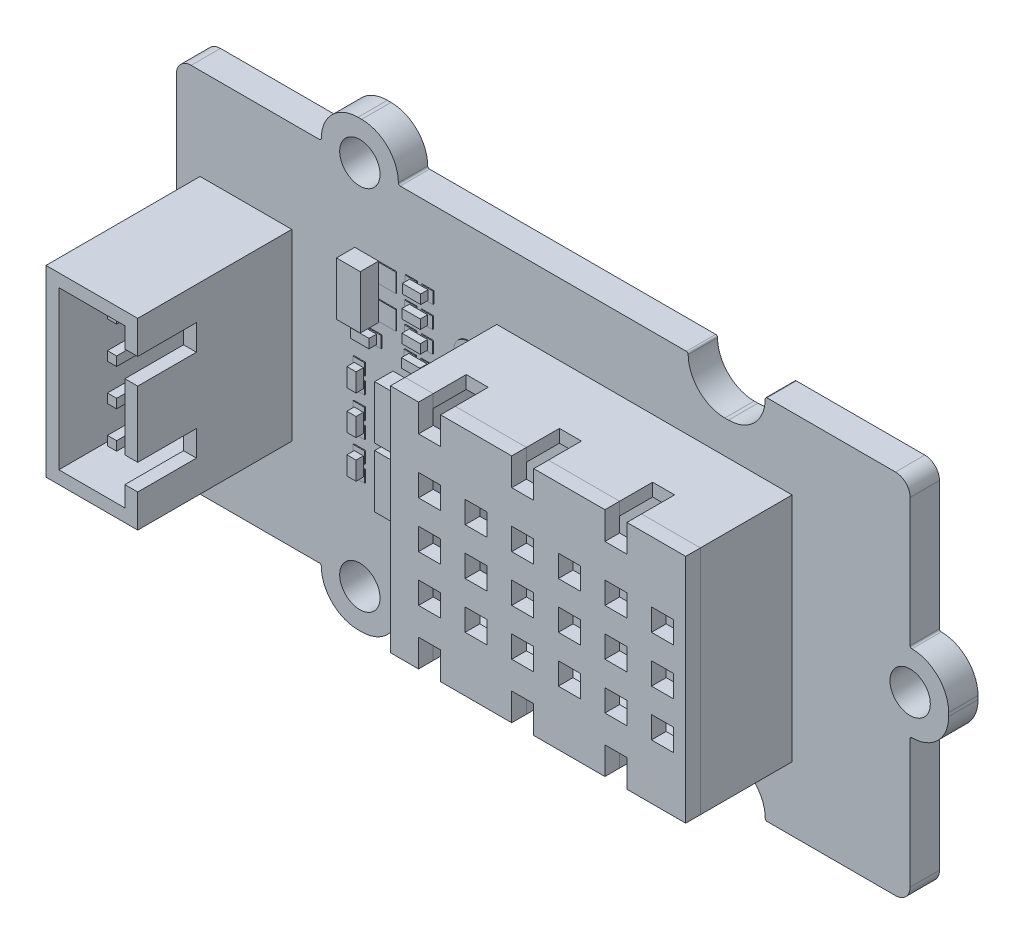
SolidWorks part; units mm, degrees
other "PCB_Grove_101020932"
ref_plane "Plan de face" through (0, 0, 0) normal (0, 0, 1) x (1, 0, 0)
ref_plane "Plan de dessus" through (0, 0, 0) normal (0, 1, 0) x (1, 0, 0)
ref_plane "Plan de droite" through (0, 0, 0) normal (1, 0, 0) x (0, 0, -1)
sketch "Esquisse1" plane through (0, 0, 0) normal (0, 0, 1) x (1, 0, 0)
  line L0 (-12.2, 10) -> (-19.2, 10)
  line L1 (-20, 9.2) -> (-20, 2.2)
  line L2 (-17.9, 0.1) -> (-17.9, -0.1)
  line L3 (-20, -2.2) -> (-20, -9.2)
  line L4 (-19.2, -10) -> (-12.2, -10)
  line L5 (-10.1, -12.1) -> (-9.9, -12.1)
  line L6 (-7.8, -10) -> (7.8, -10)
  line L7 (9.9, -7.9) -> (10.1, -7.9)
  line L8 (12.2, -10) -> (19.2, -10)
  line L9 (20, -9.2) -> (20, -2.2)
  line L10 (22.1, -0.1) -> (22.1, 0.1)
  line L11 (20, 2.2) -> (20, 9.2)
  line L12 (19.2, 10) -> (12.2, 10)
  line L13 (10.1, 7.9) -> (9.9, 7.9)
  line L14 (7.8, 10) -> (-7.8, 10)
  line L15 (-9.9, 12.1) -> (-10.1, 12.1)
  arc A0 (-19.2, 10) -> (-20, 9.2) centre (-19.2, 9.2) ccw
  arc A1 (-20, 2.2) -> (-19.9, 2.1) centre (-19.9, 2.2) ccw
  arc A2 (-19.9, 2.1) -> (-17.9, 0.1) centre (-19.9, 0.1) cw
  arc A3 (-17.9, -0.1) -> (-19.9, -2.1) centre (-19.9, -0.1) cw
  arc A4 (-19.9, -2.1) -> (-20, -2.2) centre (-19.9, -2.2) ccw
  arc A5 (-20, -9.2) -> (-19.2, -10) centre (-19.2, -9.2) ccw
  arc A6 (-12.2, -10) -> (-12.1, -10.1) centre (-12.2, -10.1) cw
  arc A7 (-12.1, -10.1) -> (-10.1, -12.1) centre (-10.1, -10.1) ccw
  arc A8 (-9.9, -12.1) -> (-7.9, -10.1) centre (-9.9, -10.1) ccw
  arc A9 (-7.9, -10.1) -> (-7.8, -10) centre (-7.8, -10.1) cw
  arc A10 (7.8, -10) -> (7.9, -9.9) centre (7.8, -9.9) ccw
  arc A11 (7.9, -9.9) -> (9.9, -7.9) centre (9.9, -9.9) cw
  arc A12 (10.1, -7.9) -> (12.1, -9.9) centre (10.1, -9.9) cw
  arc A13 (12.1, -9.9) -> (12.2, -10) centre (12.2, -9.9) ccw
  arc A14 (19.2, -10) -> (20, -9.2) centre (19.2, -9.2) ccw
  arc A15 (20, -2.2) -> (20.1, -2.1) centre (20.1, -2.2) cw
  arc A16 (20.1, -2.1) -> (22.1, -0.1) centre (20.1, -0.1) ccw
  arc A17 (22.1, 0.1) -> (20.1, 2.1) centre (20.1, 0.1) ccw
  arc A18 (20.1, 2.1) -> (20, 2.2) centre (20.1, 2.2) cw
  arc A19 (20, 9.2) -> (19.2, 10) centre (19.2, 9.2) ccw
  arc A20 (12.2, 10) -> (12.1, 9.9) centre (12.2, 9.9) ccw
  arc A21 (12.1, 9.9) -> (10.1, 7.9) centre (10.1, 9.9) cw
  arc A22 (9.9, 7.9) -> (7.9, 9.9) centre (9.9, 9.9) cw
  arc A23 (7.9, 9.9) -> (7.8, 10) centre (7.8, 9.9) ccw
  arc A24 (-7.8, 10) -> (-7.9, 10.1) centre (-7.8, 10.1) cw
  arc A25 (-7.9, 10.1) -> (-9.9, 12.1) centre (-9.9, 10.1) ccw
  arc A26 (-10.1, 12.1) -> (-12.1, 10.1) centre (-10.1, 10.1) ccw
  arc A27 (-12.1, 10.1) -> (-12.2, 10) centre (-12.2, 10.1) cw
  circle A28 centre (-10, -10) radius 1.1
  circle A29 centre (-10, 10) radius 1.1
  circle A30 centre (20, 0) radius 1.1
  circle A31 centre (-16.51, -3) radius 0.4
  circle A32 centre (-16.51, -1) radius 0.4
  circle A33 centre (-16.51, 1) radius 0.4
  circle A34 centre (-16.51, 3) radius 0.4
  circle A35 centre (-4.064, 3.81) radius 0.4445
  circle A36 centre (-4.064, 1.27) radius 0.4445
  circle A37 centre (-4.064, -1.27) radius 0.4445
  circle A38 centre (-4.064, -3.81) radius 0.4445
extrude "PCB_Eagle_V2_1_ep_ESTIMEE_1_6" add sketch "Esquisse1" along normal blind 1.6 separate body
sketch "Esquisse2" plane through (0, 0, 0) normal (0, 0, 1) x (1, 0, 0)
  line L1 (-18.71, -5) -> (-13.71, -5)
  line L2 (-18.71, -5) -> (-18.71, 5)
  line L3 (-18.71, 5) -> (-13.71, 5)
  line L4 (-13.71, -5) -> (-13.71, 5)
extrude "Grove_vertical_H_ESTIMEE" add sketch "Esquisse2" along normal blind 8.4 from offset 1.6 separate body
sketch "Esquisse3" plane through (0, 0, 0) normal (0, 0, 1) x (1, 0, 0)
  line L1 (-18.01, -4.3) -> (-14.41, -4.3)
  line L2 (-18.01, -4.3) -> (-18.01, 4.3)
  line L3 (-18.01, 4.3) -> (-14.41, 4.3)
  line L4 (-14.41, -4.3) -> (-14.41, 4.3)
extrude "Cavite_Grove" cut sketch "Esquisse3" against normal blind 7.3 from offset 10
sketch "Esquisse4" plane through (0, 0, 0) normal (0, 0, 1) x (1, 0, 0)
  line L1 (-14.51, -3.2) -> (-13.51, -3.2)
  line L2 (-14.51, -3.2) -> (-14.51, -1.8)
  line L3 (-14.51, -1.8) -> (-13.51, -1.8)
  line L4 (-13.51, -3.2) -> (-13.51, -1.8)
  line L6 (-14.51, 1.8) -> (-13.51, 1.8)
  line L7 (-14.51, 1.8) -> (-14.51, 3.2)
  line L8 (-14.51, 3.2) -> (-13.51, 3.2)
  line L9 (-13.51, 1.8) -> (-13.51, 3.2)
extrude "Detrompeurs_Grove" cut sketch "Esquisse4" against normal blind 3.2 from offset 10
sketch "Esquisse5" plane through (0, 0, 0) normal (0, 0, 1) x (1, 0, 0)
  line L1 (-16.76, -3.25) -> (-16.26, -3.25)
  line L2 (-16.76, -3.25) -> (-16.76, -2.75)
  line L3 (-16.76, -2.75) -> (-16.26, -2.75)
  line L4 (-16.26, -3.25) -> (-16.26, -2.75)
  line L6 (-16.76, -1.25) -> (-16.26, -1.25)
  line L7 (-16.76, -1.25) -> (-16.76, -0.75)
  line L8 (-16.76, -0.75) -> (-16.26, -0.75)
  line L9 (-16.26, -1.25) -> (-16.26, -0.75)
  line L11 (-16.76, 0.75) -> (-16.26, 0.75)
  line L12 (-16.76, 0.75) -> (-16.76, 1.25)
  line L13 (-16.76, 1.25) -> (-16.26, 1.25)
  line L14 (-16.26, 0.75) -> (-16.26, 1.25)
  line L16 (-16.76, 2.75) -> (-16.26, 2.75)
  line L17 (-16.76, 2.75) -> (-16.76, 3.25)
  line L18 (-16.76, 3.25) -> (-16.26, 3.25)
  line L19 (-16.26, 2.75) -> (-16.26, 3.25)
extrude "Contacts_Grove" add sketch "Esquisse5" along normal blind 9.4 from offset 0.8 separate body
sketch "Esquisse6" plane through (0, 0, 0) normal (0, 0, 1) x (1, 0, 0)
  line L1 (-2.335, -6.3) -> (13.765, -6.3)
  line L2 (-2.335, -6.3) -> (-2.335, 6.3)
  line L3 (-2.335, 6.3) -> (13.765, 6.3)
  line L4 (13.765, -6.3) -> (13.765, 6.3)
extrude "DHT20_enveloppe_16_1x12_6x5_8" add sketch "Esquisse6" along normal blind 5 from offset 1.8 separate body
sketch "Esquisse7" plane through (0, 0, 0) normal (0, 0, 1) x (1, 0, 0)
  line L1 (-1.635, -5.6) -> (13.065, -5.6)
  line L2 (-1.635, -5.6) -> (-1.635, 5.6)
  line L3 (-1.635, 5.6) -> (13.065, 5.6)
  line L4 (13.065, -5.6) -> (13.065, 5.6)
extrude "DHT20_interieur_simplifie" cut sketch "Esquisse7" against normal blind 4.4 from offset 6.8
sketch "Esquisse8" plane through (0, 0, 0) normal (0, 0, 1) x (1, 0, 0)
  line L1 (-2.335, -6.3) -> (13.765, -6.3)
  line L2 (-2.335, -6.3) -> (-2.335, 6.3)
  line L3 (-2.335, 6.3) -> (13.765, 6.3)
  line L4 (13.765, -6.3) -> (13.765, 6.3)
  line L6 (-0.8, -3.3) -> (0.4, -3.3)
  line L7 (-0.8, -3.3) -> (-0.8, -2.1)
  line L8 (-0.8, -2.1) -> (0.4, -2.1)
  line L9 (0.4, -3.3) -> (0.4, -2.1)
  line L11 (-0.8, -0.76) -> (0.4, -0.76)
  line L12 (-0.8, -0.76) -> (-0.8, 0.44)
  line L13 (-0.8, 0.44) -> (0.4, 0.44)
  line L14 (0.4, -0.76) -> (0.4, 0.44)
  line L16 (-0.8, 1.78) -> (0.4, 1.78)
  line L17 (-0.8, 1.78) -> (-0.8, 2.98)
  line L18 (-0.8, 2.98) -> (0.4, 2.98)
  line L19 (0.4, 1.78) -> (0.4, 2.98)
  line L21 (1.74, -3.3) -> (2.94, -3.3)
  line L22 (1.74, -3.3) -> (1.74, -2.1)
  line L23 (1.74, -2.1) -> (2.94, -2.1)
  line L24 (2.94, -3.3) -> (2.94, -2.1)
  line L26 (1.74, -0.76) -> (2.94, -0.76)
  line L27 (1.74, -0.76) -> (1.74, 0.44)
  line L28 (1.74, 0.44) -> (2.94, 0.44)
  line L29 (2.94, -0.76) -> (2.94, 0.44)
  line L31 (1.74, 1.78) -> (2.94, 1.78)
  line L32 (1.74, 1.78) -> (1.74, 2.98)
  line L33 (1.74, 2.98) -> (2.94, 2.98)
  line L34 (2.94, 1.78) -> (2.94, 2.98)
  line L36 (4.28, -3.3) -> (5.48, -3.3)
  line L37 (4.28, -3.3) -> (4.28, -2.1)
  line L38 (4.28, -2.1) -> (5.48, -2.1)
  line L39 (5.48, -3.3) -> (5.48, -2.1)
  line L41 (4.28, -0.76) -> (5.48, -0.76)
  line L42 (4.28, -0.76) -> (4.28, 0.44)
  line L43 (4.28, 0.44) -> (5.48, 0.44)
  line L44 (5.48, -0.76) -> (5.48, 0.44)
  line L46 (4.28, 1.78) -> (5.48, 1.78)
  line L47 (4.28, 1.78) -> (4.28, 2.98)
  line L48 (4.28, 2.98) -> (5.48, 2.98)
  line L49 (5.48, 1.78) -> (5.48, 2.98)
  line L51 (6.82, -3.3) -> (8.02, -3.3)
  line L52 (6.82, -3.3) -> (6.82, -2.1)
  line L53 (6.82, -2.1) -> (8.02, -2.1)
  line L54 (8.02, -3.3) -> (8.02, -2.1)
  line L56 (6.82, -0.76) -> (8.02, -0.76)
  line L57 (6.82, -0.76) -> (6.82, 0.44)
  line L58 (6.82, 0.44) -> (8.02, 0.44)
  line L59 (8.02, -0.76) -> (8.02, 0.44)
  line L61 (6.82, 1.78) -> (8.02, 1.78)
  line L62 (6.82, 1.78) -> (6.82, 2.98)
  line L63 (6.82, 2.98) -> (8.02, 2.98)
  line L64 (8.02, 1.78) -> (8.02, 2.98)
  line L66 (9.36, -3.3) -> (10.56, -3.3)
  line L67 (9.36, -3.3) -> (9.36, -2.1)
  line L68 (9.36, -2.1) -> (10.56, -2.1)
  line L69 (10.56, -3.3) -> (10.56, -2.1)
  line L71 (9.36, -0.76) -> (10.56, -0.76)
  line L72 (9.36, -0.76) -> (9.36, 0.44)
  line L73 (9.36, 0.44) -> (10.56, 0.44)
  line L74 (10.56, -0.76) -> (10.56, 0.44)
  line L76 (9.36, 1.78) -> (10.56, 1.78)
  line L77 (9.36, 1.78) -> (9.36, 2.98)
  line L78 (9.36, 2.98) -> (10.56, 2.98)
  line L79 (10.56, 1.78) -> (10.56, 2.98)
  line L81 (11.9, -3.3) -> (13.1, -3.3)
  line L82 (11.9, -3.3) -> (11.9, -2.1)
  line L83 (11.9, -2.1) -> (13.1, -2.1)
  line L84 (13.1, -3.3) -> (13.1, -2.1)
  line L86 (11.9, -0.76) -> (13.1, -0.76)
  line L87 (11.9, -0.76) -> (11.9, 0.44)
  line L88 (11.9, 0.44) -> (13.1, 0.44)
  line L89 (13.1, -0.76) -> (13.1, 0.44)
  line L91 (11.9, 1.78) -> (13.1, 1.78)
  line L92 (11.9, 1.78) -> (11.9, 2.98)
  line L93 (11.9, 2.98) -> (13.1, 2.98)
  line L94 (13.1, 1.78) -> (13.1, 2.98)
extrude "DHT20_grille_aeration_simplifiee" add sketch "Esquisse8" along normal blind 0.8 from offset 6.8 separate body
sketch "Esquisse9" plane through (0, 0, 0) normal (0, 0, 1) x (1, 0, 0)
  line L1 (-0.8, -6.4) -> (0.4, -6.4)
  line L2 (-0.8, -6.4) -> (-0.8, -4.8)
  line L3 (-0.8, -4.8) -> (0.4, -4.8)
  line L4 (0.4, -6.4) -> (0.4, -4.8)
  line L6 (-0.8, 4.8) -> (0.4, 4.8)
  line L7 (-0.8, 4.8) -> (-0.8, 6.4)
  line L8 (-0.8, 6.4) -> (0.4, 6.4)
  line L9 (0.4, 4.8) -> (0.4, 6.4)
  line L11 (4.28, -6.4) -> (5.48, -6.4)
  line L12 (4.28, -6.4) -> (4.28, -4.8)
  line L13 (4.28, -4.8) -> (5.48, -4.8)
  line L14 (5.48, -6.4) -> (5.48, -4.8)
  line L16 (4.28, 4.8) -> (5.48, 4.8)
  line L17 (4.28, 4.8) -> (4.28, 6.4)
  line L18 (4.28, 6.4) -> (5.48, 6.4)
  line L19 (5.48, 4.8) -> (5.48, 6.4)
  line L21 (9.36, -6.4) -> (10.56, -6.4)
  line L22 (9.36, -6.4) -> (9.36, -4.8)
  line L23 (9.36, -4.8) -> (10.56, -4.8)
  line L24 (10.56, -6.4) -> (10.56, -4.8)
  line L26 (9.36, 4.8) -> (10.56, 4.8)
  line L27 (9.36, 4.8) -> (9.36, 6.4)
  line L28 (9.36, 6.4) -> (10.56, 6.4)
  line L29 (10.56, 4.8) -> (10.56, 6.4)
extrude "DHT20_encoches_laterales" cut sketch "Esquisse9" against normal blind 2.6 from offset 7.6
sketch "Esquisse10" plane through (0, 0, 0) normal (0, 0, 1) x (1, 0, 0)
  line L1 (-4.314, -4.06) -> (-2.335, -4.06)
  line L2 (-4.314, -4.06) -> (-4.314, -3.56)
  line L3 (-4.314, -3.56) -> (-2.335, -3.56)
  line L4 (-2.335, -4.06) -> (-2.335, -3.56)
  line L6 (-4.314, -1.52) -> (-2.335, -1.52)
  line L7 (-4.314, -1.52) -> (-4.314, -1.02)
  line L8 (-4.314, -1.02) -> (-2.335, -1.02)
  line L9 (-2.335, -1.52) -> (-2.335, -1.02)
  line L11 (-4.314, 1.02) -> (-2.335, 1.02)
  line L12 (-4.314, 1.02) -> (-4.314, 1.52)
  line L13 (-4.314, 1.52) -> (-2.335, 1.52)
  line L14 (-2.335, 1.02) -> (-2.335, 1.52)
  line L16 (-4.314, 3.56) -> (-2.335, 3.56)
  line L17 (-4.314, 3.56) -> (-4.314, 4.06)
  line L18 (-4.314, 4.06) -> (-2.335, 4.06)
  line L19 (-2.335, 3.56) -> (-2.335, 4.06)
extrude "Pattes_DHT20_horizontales" add sketch "Esquisse10" along normal blind 0.3 from offset 4.05 separate body
sketch "Esquisse11" plane through (0, 0, 0) normal (0, 0, 1) x (1, 0, 0)
  line L1 (-4.314, -4.06) -> (-3.814, -4.06)
  line L2 (-4.314, -4.06) -> (-4.314, -3.56)
  line L3 (-4.314, -3.56) -> (-3.814, -3.56)
  line L4 (-3.814, -4.06) -> (-3.814, -3.56)
  line L6 (-4.314, -1.52) -> (-3.814, -1.52)
  line L7 (-4.314, -1.52) -> (-4.314, -1.02)
  line L8 (-4.314, -1.02) -> (-3.814, -1.02)
  line L9 (-3.814, -1.52) -> (-3.814, -1.02)
  line L11 (-4.314, 1.02) -> (-3.814, 1.02)
  line L12 (-4.314, 1.02) -> (-4.314, 1.52)
  line L13 (-4.314, 1.52) -> (-3.814, 1.52)
  line L14 (-3.814, 1.02) -> (-3.814, 1.52)
  line L16 (-4.314, 3.56) -> (-3.814, 3.56)
  line L17 (-4.314, 3.56) -> (-4.314, 4.06)
  line L18 (-4.314, 4.06) -> (-3.814, 4.06)
  line L19 (-3.814, 3.56) -> (-3.814, 4.06)
extrude "Pattes_DHT20_traversantes" add sketch "Esquisse11" along normal blind 4.85 from offset 0.8 separate body
sketch "Esquisse12" plane through (0, 0, 0) normal (0, 0, 1) x (1, 0, 0)
  line L1 (-10.2258, 3.0204) -> (-8.9258, 3.0204)
  line L2 (-10.2258, 3.0204) -> (-10.2258, 5.9204)
  line L3 (-10.2258, 5.9204) -> (-8.9258, 5.9204)
  line L4 (-8.9258, 3.0204) -> (-8.9258, 5.9204)
extrude "U14_position_Eagle" add sketch "Esquisse12" along normal blind 1 from offset 1.65 separate body
sketch "Esquisse13" plane through (0, 0, 0) normal (0, 0, 1) x (1, 0, 0)
  line L1 (-10.0504, 1.909) -> (-9.0504, 1.909)
  line L2 (-10.0504, 1.909) -> (-10.0504, 2.409)
  line L3 (-10.0504, 2.409) -> (-9.0504, 2.409)
  line L4 (-9.0504, 1.909) -> (-9.0504, 2.409)
extrude "C62_position_Eagle" add sketch "Esquisse13" along normal blind 0.4 from offset 1.65 separate body
sketch "Esquisse14" plane through (0, 0, 0) normal (0, 0, 1) x (1, 0, 0)
  line L1 (-7.231, 5.4142) -> (-6.231, 5.4142)
  line L2 (-7.231, 5.4142) -> (-7.231, 5.9142)
  line L3 (-7.231, 5.9142) -> (-6.231, 5.9142)
  line L4 (-6.231, 5.4142) -> (-6.231, 5.9142)
extrude "C65_position_Eagle" add sketch "Esquisse14" along normal blind 0.4 from offset 1.65 separate body
sketch "Esquisse15" plane through (0, 0, 0) normal (0, 0, 1) x (1, 0, 0)
  line L1 (-8.143, -1.7802) -> (-6.843, -1.7802)
  line L2 (-8.143, -1.7802) -> (-8.143, 1.1198)
  line L3 (-8.143, 1.1198) -> (-6.843, 1.1198)
  line L4 (-6.843, -1.7802) -> (-6.843, 1.1198)
extrude "Q12_position_Eagle" add sketch "Esquisse15" along normal blind 1 from offset 1.65 separate body
sketch "Esquisse16" plane through (0, 0, 0) normal (0, 0, 1) x (1, 0, 0)
  line L1 (-8.143, -5.0314) -> (-6.843, -5.0314)
  line L2 (-8.143, -5.0314) -> (-8.143, -2.1314)
  line L3 (-8.143, -2.1314) -> (-6.843, -2.1314)
  line L4 (-6.843, -5.0314) -> (-6.843, -2.1314)
extrude "Q13_position_Eagle" add sketch "Esquisse16" along normal blind 1 from offset 1.65 separate body
sketch "Esquisse17" plane through (0, 0, 0) normal (0, 0, 1) x (1, 0, 0)
  line L1 (-10.2576, -4.691) -> (-9.7576, -4.691)
  line L2 (-10.2576, -4.691) -> (-10.2576, -3.691)
  line L3 (-10.2576, -3.691) -> (-9.7576, -3.691)
  line L4 (-9.7576, -4.691) -> (-9.7576, -3.691)
extrude "R65_position_Eagle" add sketch "Esquisse17" along normal blind 0.4 from offset 1.65 separate body
sketch "Esquisse18" plane through (0, 0, 0) normal (0, 0, 1) x (1, 0, 0)
  line L1 (-7.2818, 1.8836) -> (-6.2818, 1.8836)
  line L2 (-7.2818, 1.8836) -> (-7.2818, 2.3836)
  line L3 (-7.2818, 2.3836) -> (-6.2818, 2.3836)
  line L4 (-6.2818, 1.8836) -> (-6.2818, 2.3836)
extrude "R66_position_Eagle" add sketch "Esquisse18" along normal blind 0.4 from offset 1.65 separate body
sketch "Esquisse19" plane through (0, 0, 0) normal (0, 0, 1) x (1, 0, 0)
  line L1 (-10.2576, -2.6336) -> (-9.7576, -2.6336)
  line L2 (-10.2576, -2.6336) -> (-10.2576, -1.6336)
  line L3 (-10.2576, -1.6336) -> (-9.7576, -1.6336)
  line L4 (-9.7576, -2.6336) -> (-9.7576, -1.6336)
extrude "R67_position_Eagle" add sketch "Esquisse19" along normal blind 0.4 from offset 1.65 separate body
sketch "Esquisse20" plane through (0, 0, 0) normal (0, 0, 1) x (1, 0, 0)
  line L1 (-10.2576, -0.5254) -> (-9.7576, -0.5254)
  line L2 (-10.2576, -0.5254) -> (-10.2576, 0.4746)
  line L3 (-10.2576, 0.4746) -> (-9.7576, 0.4746)
  line L4 (-9.7576, -0.5254) -> (-9.7576, 0.4746)
extrude "R68_position_Eagle" add sketch "Esquisse20" along normal blind 0.4 from offset 1.65 separate body
sketch "Esquisse21" plane through (0, 0, 0) normal (0, 0, 1) x (1, 0, 0)
  line L1 (-7.2564, 4.2204) -> (-6.2564, 4.2204)
  line L2 (-7.2564, 4.2204) -> (-7.2564, 4.7204)
  line L3 (-7.2564, 4.7204) -> (-6.2564, 4.7204)
  line L4 (-6.2564, 4.2204) -> (-6.2564, 4.7204)
extrude "R53_position_Eagle" add sketch "Esquisse21" along normal blind 0.4 from offset 1.65 separate body
sketch "Esquisse22" plane through (0, 0, 0) normal (0, 0, 1) x (1, 0, 0)
  line L1 (-7.2564, 3.052) -> (-6.2564, 3.052)
  line L2 (-7.2564, 3.052) -> (-7.2564, 3.552)
  line L3 (-7.2564, 3.552) -> (-6.2564, 3.552)
  line L4 (-6.2564, 3.052) -> (-6.2564, 3.552)
extrude "C54_position_Eagle" add sketch "Esquisse22" along normal blind 0.4 from offset 1.65 separate body
sketch "Esquisse23" plane through (0, 0, 0) normal (0, 0, 1) x (1, 0, 0)
  circle A0 centre (-16.51, -3) radius 0.635
  circle A1 centre (-16.51, -3) radius 0.4
extrude "Anneau_J8_0" add sketch "Esquisse23" along normal blind 0.05 from offset 1.6 separate body
sketch "Esquisse24" plane through (0, 0, 0) normal (0, 0, 1) x (1, 0, 0)
  circle A0 centre (-16.51, -1) radius 0.635
  circle A1 centre (-16.51, -1) radius 0.4
extrude "Anneau_J8_1" add sketch "Esquisse24" along normal blind 0.05 from offset 1.6 separate body
sketch "Esquisse25" plane through (0, 0, 0) normal (0, 0, 1) x (1, 0, 0)
  circle A0 centre (-16.51, 1) radius 0.635
  circle A1 centre (-16.51, 1) radius 0.4
extrude "Anneau_J8_2" add sketch "Esquisse25" along normal blind 0.05 from offset 1.6 separate body
sketch "Esquisse26" plane through (0, 0, 0) normal (0, 0, 1) x (1, 0, 0)
  circle A0 centre (-16.51, 3) radius 0.635
  circle A1 centre (-16.51, 3) radius 0.4
extrude "Anneau_J8_3" add sketch "Esquisse26" along normal blind 0.05 from offset 1.6 separate body
sketch "Esquisse27" plane through (0, 0, 0) normal (0, 0, 1) x (1, 0, 0)
  circle A0 centre (-4.064, 3.81) radius 0.762
  circle A1 centre (-4.064, 3.81) radius 0.4445
extrude "Anneau_U11_0" add sketch "Esquisse27" along normal blind 0.05 from offset 1.6 separate body
sketch "Esquisse28" plane through (0, 0, 0) normal (0, 0, 1) x (1, 0, 0)
  circle A0 centre (-4.064, 1.27) radius 0.762
  circle A1 centre (-4.064, 1.27) radius 0.4445
extrude "Anneau_U11_1" add sketch "Esquisse28" along normal blind 0.05 from offset 1.6 separate body
sketch "Esquisse29" plane through (0, 0, 0) normal (0, 0, 1) x (1, 0, 0)
  circle A0 centre (-4.064, -1.27) radius 0.762
  circle A1 centre (-4.064, -1.27) radius 0.4445
extrude "Anneau_U11_2" add sketch "Esquisse29" along normal blind 0.05 from offset 1.6 separate body
sketch "Esquisse30" plane through (0, 0, 0) normal (0, 0, 1) x (1, 0, 0)
  circle A0 centre (-4.064, -3.81) radius 0.762
  circle A1 centre (-4.064, -3.81) radius 0.4445
extrude "Anneau_U11_3" add sketch "Esquisse30" along normal blind 0.05 from offset 1.6 separate body
sketch "Esquisse31" plane through (0, 0, 0) normal (0, 0, 1) x (1, 0, 0)
  line L1 (-11.1633, 3.9624) -> (-10.0203, 3.9624)
  line L2 (-11.1633, 3.9624) -> (-11.1633, 4.9784)
  line L3 (-11.1633, 4.9784) -> (-10.0203, 4.9784)
  line L4 (-10.0203, 3.9624) -> (-10.0203, 4.9784)
extrude "Pad_U14_0" add sketch "Esquisse31" along normal blind 0.05 from offset 1.6 separate body
sketch "Esquisse32" plane through (0, 0, 0) normal (0, 0, 1) x (1, 0, 0)
  line L1 (-9.1313, 4.8514) -> (-7.9883, 4.8514)
  line L2 (-9.1313, 4.8514) -> (-9.1313, 5.8674)
  line L3 (-9.1313, 5.8674) -> (-7.9883, 5.8674)
  line L4 (-7.9883, 4.8514) -> (-7.9883, 5.8674)
extrude "Pad_U14_1" add sketch "Esquisse32" along normal blind 0.05 from offset 1.6 separate body
sketch "Esquisse33" plane through (0, 0, 0) normal (0, 0, 1) x (1, 0, 0)
  line L1 (-9.1313, 3.0734) -> (-7.9883, 3.0734)
  line L2 (-9.1313, 3.0734) -> (-9.1313, 4.0894)
  line L3 (-9.1313, 4.0894) -> (-7.9883, 4.0894)
  line L4 (-7.9883, 3.0734) -> (-7.9883, 4.0894)
extrude "Pad_U14_2" add sketch "Esquisse33" along normal blind 0.05 from offset 1.6 separate body
sketch "Esquisse34" plane through (0, 0, 0) normal (0, 0, 1) x (1, 0, 0)
  line L1 (-10.3124, 1.8415) -> (-9.6774, 1.8415)
  line L2 (-10.3124, 1.8415) -> (-10.3124, 2.4765)
  line L3 (-10.3124, 2.4765) -> (-9.6774, 2.4765)
  line L4 (-9.6774, 1.8415) -> (-9.6774, 2.4765)
extrude "Pad_C62_0" add sketch "Esquisse34" along normal blind 0.05 from offset 1.6 separate body
sketch "Esquisse35" plane through (0, 0, 0) normal (0, 0, 1) x (1, 0, 0)
  line L1 (-9.4234, 1.8415) -> (-8.7884, 1.8415)
  line L2 (-9.4234, 1.8415) -> (-9.4234, 2.4765)
  line L3 (-9.4234, 2.4765) -> (-8.7884, 2.4765)
  line L4 (-8.7884, 1.8415) -> (-8.7884, 2.4765)
extrude "Pad_C62_1" add sketch "Esquisse35" along normal blind 0.05 from offset 1.6 separate body
sketch "Esquisse36" plane through (0, 0, 0) normal (0, 0, 1) x (1, 0, 0)
  line L1 (-7.493, 5.3467) -> (-6.858, 5.3467)
  line L2 (-7.493, 5.3467) -> (-7.493, 5.9817)
  line L3 (-7.493, 5.9817) -> (-6.858, 5.9817)
  line L4 (-6.858, 5.3467) -> (-6.858, 5.9817)
extrude "Pad_C65_0" add sketch "Esquisse36" along normal blind 0.05 from offset 1.6 separate body
sketch "Esquisse37" plane through (0, 0, 0) normal (0, 0, 1) x (1, 0, 0)
  line L1 (-6.604, 5.3467) -> (-5.969, 5.3467)
  line L2 (-6.604, 5.3467) -> (-6.604, 5.9817)
  line L3 (-6.604, 5.9817) -> (-5.969, 5.9817)
  line L4 (-5.969, 5.3467) -> (-5.969, 5.9817)
extrude "Pad_C65_1" add sketch "Esquisse37" along normal blind 0.05 from offset 1.6 separate body
sketch "Esquisse38" plane through (0, 0, 0) normal (0, 0, 1) x (1, 0, 0)
  line L1 (-9.0805, -0.8382) -> (-7.9375, -0.8382)
  line L2 (-9.0805, -0.8382) -> (-9.0805, 0.1778)
  line L3 (-9.0805, 0.1778) -> (-7.9375, 0.1778)
  line L4 (-7.9375, -0.8382) -> (-7.9375, 0.1778)
extrude "Pad_Q12_0" add sketch "Esquisse38" along normal blind 0.05 from offset 1.6 separate body
sketch "Esquisse39" plane through (0, 0, 0) normal (0, 0, 1) x (1, 0, 0)
  line L1 (-7.0485, 0.0508) -> (-5.9055, 0.0508)
  line L2 (-7.0485, 0.0508) -> (-7.0485, 1.0668)
  line L3 (-7.0485, 1.0668) -> (-5.9055, 1.0668)
  line L4 (-5.9055, 0.0508) -> (-5.9055, 1.0668)
extrude "Pad_Q12_1" add sketch "Esquisse39" along normal blind 0.05 from offset 1.6 separate body
sketch "Esquisse40" plane through (0, 0, 0) normal (0, 0, 1) x (1, 0, 0)
  line L1 (-7.0485, -1.7272) -> (-5.9055, -1.7272)
  line L2 (-7.0485, -1.7272) -> (-7.0485, -0.7112)
  line L3 (-7.0485, -0.7112) -> (-5.9055, -0.7112)
  line L4 (-5.9055, -1.7272) -> (-5.9055, -0.7112)
extrude "Pad_Q12_2" add sketch "Esquisse40" along normal blind 0.05 from offset 1.6 separate body
sketch "Esquisse41" plane through (0, 0, 0) normal (0, 0, 1) x (1, 0, 0)
  line L1 (-9.0805, -4.0894) -> (-7.9375, -4.0894)
  line L2 (-9.0805, -4.0894) -> (-9.0805, -3.0734)
  line L3 (-9.0805, -3.0734) -> (-7.9375, -3.0734)
  line L4 (-7.9375, -4.0894) -> (-7.9375, -3.0734)
extrude "Pad_Q13_0" add sketch "Esquisse41" along normal blind 0.05 from offset 1.6 separate body
sketch "Esquisse42" plane through (0, 0, 0) normal (0, 0, 1) x (1, 0, 0)
  line L1 (-7.0485, -3.2004) -> (-5.9055, -3.2004)
  line L2 (-7.0485, -3.2004) -> (-7.0485, -2.1844)
  line L3 (-7.0485, -2.1844) -> (-5.9055, -2.1844)
  line L4 (-5.9055, -3.2004) -> (-5.9055, -2.1844)
extrude "Pad_Q13_1" add sketch "Esquisse42" along normal blind 0.05 from offset 1.6 separate body
sketch "Esquisse43" plane through (0, 0, 0) normal (0, 0, 1) x (1, 0, 0)
  line L1 (-7.0485, -4.9784) -> (-5.9055, -4.9784)
  line L2 (-7.0485, -4.9784) -> (-7.0485, -3.9624)
  line L3 (-7.0485, -3.9624) -> (-5.9055, -3.9624)
  line L4 (-5.9055, -4.9784) -> (-5.9055, -3.9624)
extrude "Pad_Q13_2" add sketch "Esquisse43" along normal blind 0.05 from offset 1.6 separate body
sketch "Esquisse44" plane through (0, 0, 0) normal (0, 0, 1) x (1, 0, 0)
  line L1 (-10.3251, -4.953) -> (-9.6901, -4.953)
  line L2 (-10.3251, -4.953) -> (-10.3251, -4.318)
  line L3 (-10.3251, -4.318) -> (-9.6901, -4.318)
  line L4 (-9.6901, -4.953) -> (-9.6901, -4.318)
extrude "Pad_R65_0" add sketch "Esquisse44" along normal blind 0.05 from offset 1.6 separate body
sketch "Esquisse45" plane through (0, 0, 0) normal (0, 0, 1) x (1, 0, 0)
  line L1 (-10.3251, -4.064) -> (-9.6901, -4.064)
  line L2 (-10.3251, -4.064) -> (-10.3251, -3.429)
  line L3 (-10.3251, -3.429) -> (-9.6901, -3.429)
  line L4 (-9.6901, -4.064) -> (-9.6901, -3.429)
extrude "Pad_R65_1" add sketch "Esquisse45" along normal blind 0.05 from offset 1.6 separate body
sketch "Esquisse46" plane through (0, 0, 0) normal (0, 0, 1) x (1, 0, 0)
  line L1 (-7.5438, 1.8161) -> (-6.9088, 1.8161)
  line L2 (-7.5438, 1.8161) -> (-7.5438, 2.4511)
  line L3 (-7.5438, 2.4511) -> (-6.9088, 2.4511)
  line L4 (-6.9088, 1.8161) -> (-6.9088, 2.4511)
extrude "Pad_R66_0" add sketch "Esquisse46" along normal blind 0.05 from offset 1.6 separate body
sketch "Esquisse47" plane through (0, 0, 0) normal (0, 0, 1) x (1, 0, 0)
  line L1 (-6.6548, 1.8161) -> (-6.0198, 1.8161)
  line L2 (-6.6548, 1.8161) -> (-6.6548, 2.4511)
  line L3 (-6.6548, 2.4511) -> (-6.0198, 2.4511)
  line L4 (-6.0198, 1.8161) -> (-6.0198, 2.4511)
extrude "Pad_R66_1" add sketch "Esquisse47" along normal blind 0.05 from offset 1.6 separate body
sketch "Esquisse48" plane through (0, 0, 0) normal (0, 0, 1) x (1, 0, 0)
  line L1 (-10.3251, -2.0066) -> (-9.6901, -2.0066)
  line L2 (-10.3251, -2.0066) -> (-10.3251, -1.3716)
  line L3 (-10.3251, -1.3716) -> (-9.6901, -1.3716)
  line L4 (-9.6901, -2.0066) -> (-9.6901, -1.3716)
extrude "Pad_R67_0" add sketch "Esquisse48" along normal blind 0.05 from offset 1.6 separate body
sketch "Esquisse49" plane through (0, 0, 0) normal (0, 0, 1) x (1, 0, 0)
  line L1 (-10.3251, -2.8956) -> (-9.6901, -2.8956)
  line L2 (-10.3251, -2.8956) -> (-10.3251, -2.2606)
  line L3 (-10.3251, -2.2606) -> (-9.6901, -2.2606)
  line L4 (-9.6901, -2.8956) -> (-9.6901, -2.2606)
extrude "Pad_R67_1" add sketch "Esquisse49" along normal blind 0.05 from offset 1.6 separate body
sketch "Esquisse50" plane through (0, 0, 0) normal (0, 0, 1) x (1, 0, 0)
  line L1 (-10.3251, 0.1016) -> (-9.6901, 0.1016)
  line L2 (-10.3251, 0.1016) -> (-10.3251, 0.7366)
  line L3 (-10.3251, 0.7366) -> (-9.6901, 0.7366)
  line L4 (-9.6901, 0.1016) -> (-9.6901, 0.7366)
extrude "Pad_R68_0" add sketch "Esquisse50" along normal blind 0.05 from offset 1.6 separate body
sketch "Esquisse51" plane through (0, 0, 0) normal (0, 0, 1) x (1, 0, 0)
  line L1 (-10.3251, -0.7874) -> (-9.6901, -0.7874)
  line L2 (-10.3251, -0.7874) -> (-10.3251, -0.1524)
  line L3 (-10.3251, -0.1524) -> (-9.6901, -0.1524)
  line L4 (-9.6901, -0.7874) -> (-9.6901, -0.1524)
extrude "Pad_R68_1" add sketch "Esquisse51" along normal blind 0.05 from offset 1.6 separate body
sketch "Esquisse52" plane through (0, 0, 0) normal (0, 0, 1) x (1, 0, 0)
  line L1 (-6.6294, 4.1529) -> (-5.9944, 4.1529)
  line L2 (-6.6294, 4.1529) -> (-6.6294, 4.7879)
  line L3 (-6.6294, 4.7879) -> (-5.9944, 4.7879)
  line L4 (-5.9944, 4.1529) -> (-5.9944, 4.7879)
extrude "Pad_R53_0" add sketch "Esquisse52" along normal blind 0.05 from offset 1.6 separate body
sketch "Esquisse53" plane through (0, 0, 0) normal (0, 0, 1) x (1, 0, 0)
  line L1 (-7.5184, 4.1529) -> (-6.8834, 4.1529)
  line L2 (-7.5184, 4.1529) -> (-7.5184, 4.7879)
  line L3 (-7.5184, 4.7879) -> (-6.8834, 4.7879)
  line L4 (-6.8834, 4.1529) -> (-6.8834, 4.7879)
extrude "Pad_R53_1" add sketch "Esquisse53" along normal blind 0.05 from offset 1.6 separate body
sketch "Esquisse54" plane through (0, 0, 0) normal (0, 0, 1) x (1, 0, 0)
  line L1 (-7.5184, 2.9845) -> (-6.8834, 2.9845)
  line L2 (-7.5184, 2.9845) -> (-7.5184, 3.6195)
  line L3 (-7.5184, 3.6195) -> (-6.8834, 3.6195)
  line L4 (-6.8834, 2.9845) -> (-6.8834, 3.6195)
extrude "Pad_C54_0" add sketch "Esquisse54" along normal blind 0.05 from offset 1.6 separate body
sketch "Esquisse55" plane through (0, 0, 0) normal (0, 0, 1) x (1, 0, 0)
  line L1 (-6.6294, 2.9845) -> (-5.9944, 2.9845)
  line L2 (-6.6294, 2.9845) -> (-6.6294, 3.6195)
  line L3 (-6.6294, 3.6195) -> (-5.9944, 3.6195)
  line L4 (-5.9944, 2.9845) -> (-5.9944, 3.6195)
extrude "Pad_C54_1" add sketch "Esquisse55" along normal blind 0.05 from offset 1.6 separate body
